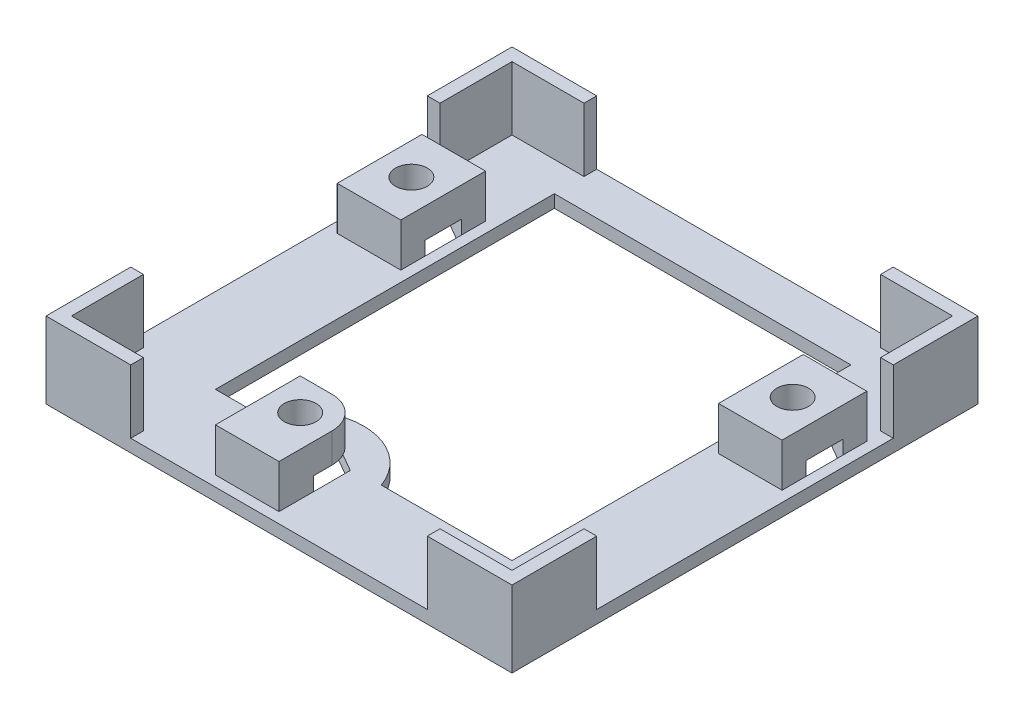
SolidWorks part; units mm, degrees
ref_plane "Front Plane" through (0, 0, 0) normal (0, 0, 1) x (1, 0, 0)
ref_plane "Top Plane" through (0, 0, 0) normal (0, 1, 0) x (1, 0, 0)
ref_plane "Right Plane" through (0, 0, 0) normal (1, 0, 0) x (0, 0, -1)
sketch "Sketch1" plane through (0, 0, 0) normal (0, 1, 0) x (1, 0, 0)
  line L0 (23.6569, 8) -> (36, 8)
  line L1 (0, 0) -> (44, 0)
  line L2 (0, 0) -> (0, 44)
  line L3 (0, 44) -> (44, 44)
  line L4 (44, 0) -> (44, 44)
  line L5 (1, 32.2321) -> (1, 28.7679)
  line L6 (1, 28.7679) -> (4, 27.0359)
  line L7 (4, 27.0359) -> (7, 28.7679)
  line L8 (7, 28.7679) -> (7, 32.2321)
  line L9 (7, 32.2321) -> (4, 33.9641)
  line L10 (4, 33.9641) -> (1, 32.2321)
  line L11 (37, 32.2321) -> (37, 28.7679)
  line L12 (37, 28.7679) -> (40, 27.0359)
  line L13 (40, 27.0359) -> (43, 28.7679)
  line L14 (43, 28.7679) -> (43, 32.2321)
  line L15 (43, 32.2321) -> (40, 33.9641)
  line L16 (40, 33.9641) -> (37, 32.2321)
  line L17 (15, 7.7321) -> (15, 4.2679)
  line L18 (15, 4.2679) -> (18, 2.5359)
  line L19 (18, 2.5359) -> (21, 4.2679)
  line L20 (21, 4.2679) -> (21, 7.7321)
  line L21 (21, 7.7321) -> (18, 9.4641)
  line L22 (18, 9.4641) -> (15, 7.7321)
  line L23 (8, 40) -> (36, 40)
  line L24 (8, 40) -> (8, 8)
  line L25 (8, 8) -> (12.3431, 8)
  line L26 (36, 40) -> (36, 8)
  circle A0 centre (4, 30.5) radius 1.5
  circle A1 centre (40, 30.5) radius 1.5
  circle A2 centre (18, 6) radius 1.5
  circle A3 centre (4, 30.5) radius 3 construction
  circle A4 centre (40, 30.5) radius 3 construction
  circle A5 centre (18, 6) radius 3 construction
  arc A6 (23.6569, 8) -> (12.3431, 8) centre (18, 6) ccw
  dimension "D3" = 3
  dimension "D16" = 12
  dimension "D1" = 44
  dimension "D2" = 44
  dimension "D4" = 36
  dimension "D5" = 24.5
  dimension "D6" = 14
  dimension "D7" = 6
  dimension "D8" = 6
  dimension "D9" = 6
  dimension "D10" = 4
  dimension "D11" = 6
  dimension "D12" = 8
  dimension "D13" = 8
  dimension "D14" = 4
  dimension "D15" = 8
extrude "Boss-Extrude1" add sketch "Sketch1" along normal blind 1.2 contours L1 L4 L3 L2 L22 L21 L20 L19 L18 L17 L16 L15 L14 L13 L12 L11 L10 L9 L8 L7 L6 L5 L0 A6 L25 L24 L23 L26 | L21 L22 L17 L18 L19 L20 A2 | L15 L16 L11 L12 L13 L14 A1 | L9 L10 L5 L6 L7 L8 A0 region at (0.6223, 0, -22) region at (2.5458, 0, -33.0187) region at (38.5458, 0, -33.0187) region at (16.5458, 0, -8.5187)
sketch "Sketch4" plane through (0, 1.2, 0) normal (0, 1, 0) x (1, 0, 0)
  line L1 (0, 44) -> (8, 44)
  line L2 (0, 44) -> (0, 42.8)
  line L3 (0, 42.8) -> (8, 42.8)
  line L4 (8, 44) -> (8, 42.8)
  line L5 (0, 42.8) -> (1.2, 42.8)
  line L6 (0, 42.8) -> (0, 36)
  line L7 (0, 36) -> (1.2, 36)
  line L8 (1.2, 42.8) -> (1.2, 36)
  line L9 (44, 44) -> (36, 44)
  line L10 (44, 44) -> (44, 42.8)
  line L11 (44, 42.8) -> (36, 42.8)
  line L12 (36, 44) -> (36, 42.8)
  line L13 (44, 42.8) -> (42.8, 42.8)
  line L14 (44, 42.8) -> (44, 36)
  line L15 (44, 36) -> (42.8, 36)
  line L16 (42.8, 42.8) -> (42.8, 36)
  line L17 (44, 0) -> (36, 0)
  line L18 (44, 0) -> (44, 1.2)
  line L19 (44, 1.2) -> (36, 1.2)
  line L20 (36, 0) -> (36, 1.2)
  line L21 (44, 1.2) -> (42.8, 1.2)
  line L22 (44, 1.2) -> (44, 8)
  line L23 (44, 8) -> (42.8, 8)
  line L24 (42.8, 1.2) -> (42.8, 8)
  line L25 (0, 0) -> (8, 0)
  line L26 (0, 0) -> (0, 1.2)
  line L27 (0, 1.2) -> (8, 1.2)
  line L28 (8, 0) -> (8, 1.2)
  line L29 (0, 1.2) -> (1.2, 1.2)
  line L30 (0, 1.2) -> (0, 8)
  line L31 (0, 8) -> (1.2, 8)
  line L32 (1.2, 1.2) -> (1.2, 8)
  line M31 (0, 0) -> (44, 0)
  line M32 (44, 0) -> (44, 44)
  line M33 (44, 44) -> (0, 44)
  line M34 (0, 44) -> (0, 0)
  dimension "D1" = 8
  dimension "8" = 8
  dimension "D3" = 8
  dimension "D4" = 8
  dimension "D5" = 1.2
  dimension "D6" = 1.2
  dimension "D7" = 1.2
  dimension "D8" = 1.2
  dimension "D9" = 8
  dimension "D10" = 8
  dimension "D11" = 8
  dimension "D12" = 8
extrude "Boss-Extrude4" add sketch "Sketch4" along normal blind 6 contours L4 L3 M33 M34 | L12 L11 M33 M32 | L11 L16 L15 M32 | L8 L3 L7 M34 | L27 L32 L31 M34 | L28 L27 M31 M34 | L24 L19 L23 M32 | L19 L20 L17 L18 region at (4, 1.2, -43.4) region at (0.6, 1.2, -39.4) region at (40, 1.2, -43.4) region at (0.6, 1.2, -4.6) region at (43.4, 1.2, -39.4) region at (4, 1.2, -0.6) region at (43.4, 1.2, -4.6)
sketch "Sketch5" plane through (0, 1.2, 0) normal (0, 1, 0) x (1, 0, 0)
  line L0 (0, 8) -> (0, 36) construction
  line L1 (1, 34.5) -> (7, 34.5)
  line L2 (1, 34.5) -> (1, 26.5)
  line L3 (1, 26.5) -> (7, 26.5)
  line L4 (7, 34.5) -> (7, 26.5)
  line L5 (37, 34.5) -> (43, 34.5)
  line L6 (37, 34.5) -> (37, 26.5)
  line L7 (37, 26.5) -> (43, 26.5)
  line L8 (43, 34.5) -> (43, 26.5)
  line L13 (44, 8) -> (44, 36) construction
  line L15 (8, 0) -> (36, 0) construction
  line L16 (15, 9) -> (18, 9)
  line L17 (15, 9) -> (15, 1)
  line L18 (15, 1) -> (21, 1)
  line L19 (21, 6) -> (21, 1)
  arc A1 (18, 9) -> (21, 6) centre (18, 6) cw
  point P8 (0, 0)
  point P9 (7, 30.5)
  point P26 (4, 34.5)
  point P30 (21, 9)
  dimension "D17" = 3
  dimension "D1" = 6
  dimension "D2" = 6
  dimension "D3" = 8
  dimension "D4" = 8
  dimension "D5" = 1
  dimension "D6" = 1
  dimension "D7" = 24.5
  dimension "D13" = 1
  dimension "D14" = 8
  dimension "D15" = 6
  dimension "D16" = 14
extrude "Boss-Extrude8" add sketch "Sketch5" along normal blind 4.1
extrude "Cut-Extrude1" cut sketch "Sketch1<3>" along normal blind 2.5 contours L9 L10 L5 L6 L7 L8 A0 | L21 L22 L17 L18 L19 L20 A2 | L15 L16 L11 L12 L13 L14 A1 region at (2.5458, 0, -33.0187) region at (38.5458, 0, -33.0187) region at (16.5458, 0, -8.5187)
sketch "Sketch1<3>" plane through (0, 0, 0) normal (0, 1, 0) x (1, 0, 0) same geometry as "Sketch1"
extrude "Cut-Extrude2" cut sketch "Sketch1<4>" along normal through all contours A0 | A2 | A1 region at (4, 0, -30.5) region at (40, 0, -30.5) region at (18, 0, -6)
sketch "Sketch1<4>" plane through (0, 0, 0) normal (0, 1, 0) x (1, 0, 0) same geometry as "Sketch1"
